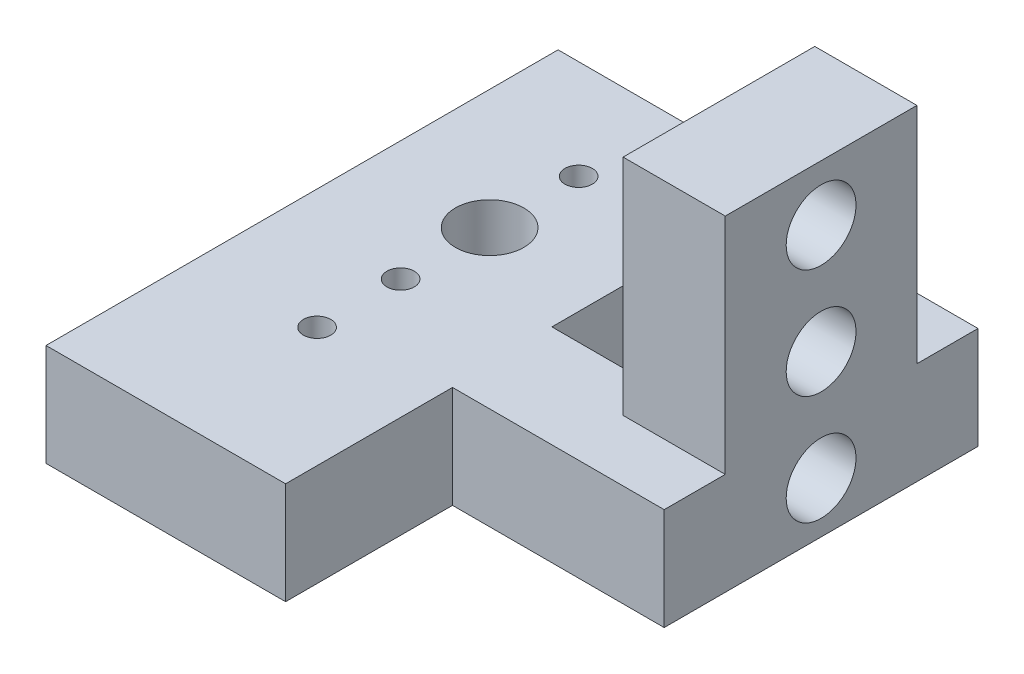
SolidWorks part; units mm, degrees
ref_plane "Front Plane" through (0, 0, 0) normal (0, 0, 1) x (1, 0, 0)
ref_plane "Top Plane" through (0, 0, 0) normal (0, 1, 0) x (1, 0, 0)
ref_plane "Right Plane" through (0, 0, 0) normal (1, 0, 0) x (0, 0, -1)
sketch "Sketch1" plane through (0, 0, 0) normal (0, 1, 0) x (1, 0, 0)
  line L0 (0, 95.561) -> (0, -103.6026) construction
  line L1 (-120.0879, 0) -> (122.2323, 0) construction
  line B0 (0, 24.3119) -> (0, -27.7936) construction
  line B1 (-27.8941, 0) -> (23.9754, 0) construction
  line B2 (8.75, 11.46) -> (24.21, 11.46)
  line B3 (8.55, 4) -> (16.75, 4)
  line B4 (8.55, 4) -> (8.55, -4)
  line B5 (8.55, -4) -> (16.75, -4)
  line B6 (16.75, 4) -> (16.75, -4)
  line B7 (8.55, 4) -> (16.75, -4) construction
  line B8 (8.55, -4) -> (16.75, 4) construction
  line B9 (-8.75, 13.75) -> (8.75, 13.75)
  line B10 (-8.75, 13.75) -> (-8.75, -23.65)
  line B11 (-8.75, -23.65) -> (8.75, -23.65)
  line B12 (8.75, 13.75) -> (8.75, 11.46)
  line B13 (-8.75, 13.75) -> (8.75, -23.65) construction
  line B14 (-8.75, -23.65) -> (8.75, 13.75) construction
  line B15 (24.21, 11.46) -> (24.21, -11.46)
  line B16 (8.75, -11.46) -> (24.21, -11.46)
  line B17 (8.75, -11.46) -> (8.75, -23.65)
  dimension "D1" = 0
  dimension "D2" = 0
sketch_block_instance "Block3-1"
sketch_block "Block3" parameters "D1"=8.2, "D2"=8, "D3"=12.65, "D4"=7.46, "D5"=7.46
extrude "Boss-Extrude1" add sketch "Sketch1" along normal blind 7.46
sketch "Sketch3" plane through (0, 7.46, 0) normal (0, 1, 0) x (1, 0, 0)
  line L0 (16.75, 0) -> (24.21, 0) construction
  line L1 (16.75, -4) -> (16.75, 4) construction
  line L2 (24.21, -11.46) -> (24.21, 11.46) construction
  line L3 (16.75, 7) -> (24.21, 7)
  line L4 (16.75, -7) -> (24.21, -7)
  line L5 (16.75, -7) -> (16.75, -4)
  line L6 (16.75, 4) -> (16.75, 7)
  line L7 (16.75, -4) -> (16.75, 4)
  line L8 (24.21, -7) -> (24.21, 7)
  dimension "D1" = 7
extrude "Boss-Extrude2" add sketch "Sketch3" along normal blind 16.34
sketch "Sketch4" plane through (16.75, 0, 0) normal (-1, 0, 0) x (0, 0, 1)
  line L0 (-4, 3.73) -> (4, 3.73) construction
  line L1 (-4, 7.46) -> (-4, 0) construction
  line L2 (4, 7.46) -> (4, 0) construction
  line L3 (0, 0) -> (0, 23.8) construction
  line L4 (4, 0) -> (-4, 0) construction
  line L5 (-7, 23.8) -> (7, 23.8) construction
  circle A0 centre (0, 3.73) radius 2.55
  circle A1 centre (0, 11.73) radius 2.55
  circle A2 centre (0, 19.73) radius 2.55
  dimension "D1" = 5.1
  dimension "D3" = 8
  dimension "D2" = 3
extrude "Cut-Extrude1" cut sketch "Sketch4" against normal through all
sketch "Sketch5" plane through (0, 0, 0) normal (0, -1, 0) x (1, 0, 0)
  line L0 (8.55, 0) -> (-8.75, 0) construction
  line L1 (8.55, -4) -> (8.55, 4) construction
  line L2 (-8.75, -13.75) -> (-8.75, 23.65) construction
  line L3 (0, -13.75) -> (0, 23.65) construction
  line L4 (8.75, -13.75) -> (-8.75, -13.75) construction
  line L5 (-8.75, 23.65) -> (8.75, 23.65) construction
  line B0 (4.9, 0) -> (-4.9, 0) construction
  line B1 (0, 18) -> (0, -18) construction
  line B2 (4.9, 14.75) -> (-5.1593, 14.75) construction
  line B3 (4.9, -14.75) -> (-5.1593, -14.75) construction
  line B4 (-2.114, 14.9661) -> (-3.6062, 0.3686)
  line B5 (-3.6062, -0.3686) -> (-2.114, -14.9661)
  line B6 (2.114, -14.9661) -> (3.6062, -0.3686)
  line B7 (2.114, 14.9661) -> (3.6062, 0.3686)
  arc B8 (2.114, 14.9661) -> (-2.114, 14.9661) centre (0, 14.75) ccw
  arc B9 (-3.6062, 0.3686) -> (-3.6062, -0.3686) centre (0, 0) ccw
  arc B10 (2.114, -14.9661) -> (-2.114, -14.9661) centre (0, -14.75) cw
  arc B11 (3.6062, -0.3686) -> (3.6062, 0.3686) centre (0, 0) ccw
  dimension "D2" = 0
  dimension "D1" = 0
sketch_block_instance "Block5-1"
sketch_block "Block5" parameters "D2"=4.25, "D3"=7.25, "D1"=14.75
extrude "Cut-Extrude2" cut sketch "Sketch5" against normal blind 2
sketch "Sketch6" plane through (0, 2, 0) normal (0, -1, 0) x (1, 0, 0)
  line L0 (0, 0) -> (-3.625, 0) construction
  line L1 (0, 0) -> (0, 16.875) construction
  line L2 (0, 6.5) -> (1.6708, 6.5) construction
  line L3 (0, 12.6) -> (1.6708, 12.6) construction
  line L4 (0, 0) -> (0, -13.75) construction
  line L5 (-2.2383, -13.75) -> (2.2383, -13.75) construction
  line L6 (0, -6.5) -> (1.6708, -6.5) construction
  arc A0 (-3.6062, 0.3686) -> (-3.6062, -0.3686) centre (0, 0) ccw construction
  arc A1 (2.114, 14.9661) -> (-2.114, 14.9661) centre (0, 14.75) ccw construction
  circle A2 centre (0, 12.6) radius 1
  circle A3 centre (0, 6.5) radius 1
  circle A4 centre (0, -6.5) radius 1
  dimension "D3" = 2
  dimension "D4" = 2
  dimension "D7" = 2
  dimension "D1" = 6.5
  dimension "D2" = 12.6
  dimension "D5" = 6.5
extrude "Cut-Extrude4" cut sketch "Sketch6" against normal up to next
sketch "Sketch7" plane through (0, 2, 0) normal (0, -1, 0) x (1, 0, 0)
  line L0 (3.625, 0) -> (-3.625, 0) construction
  line L1 (0, 16.875) -> (0, -13.75) construction
  line L2 (-2.2383, -13.75) -> (2.2383, -13.75) construction
  arc A0 (3.6062, -0.3686) -> (3.6062, 0.3686) centre (0, 0) ccw construction
  arc A1 (-3.6062, 0.3686) -> (-3.6062, -0.3686) centre (0, 0) ccw construction
  arc A2 (2.114, 14.9661) -> (-2.114, 14.9661) centre (0, 14.75) ccw construction
  circle A3 centre (0, 0) radius 2.5
  dimension "D1" = 5
extrude "Cut-Extrude5" cut sketch "Sketch7" against normal through all
